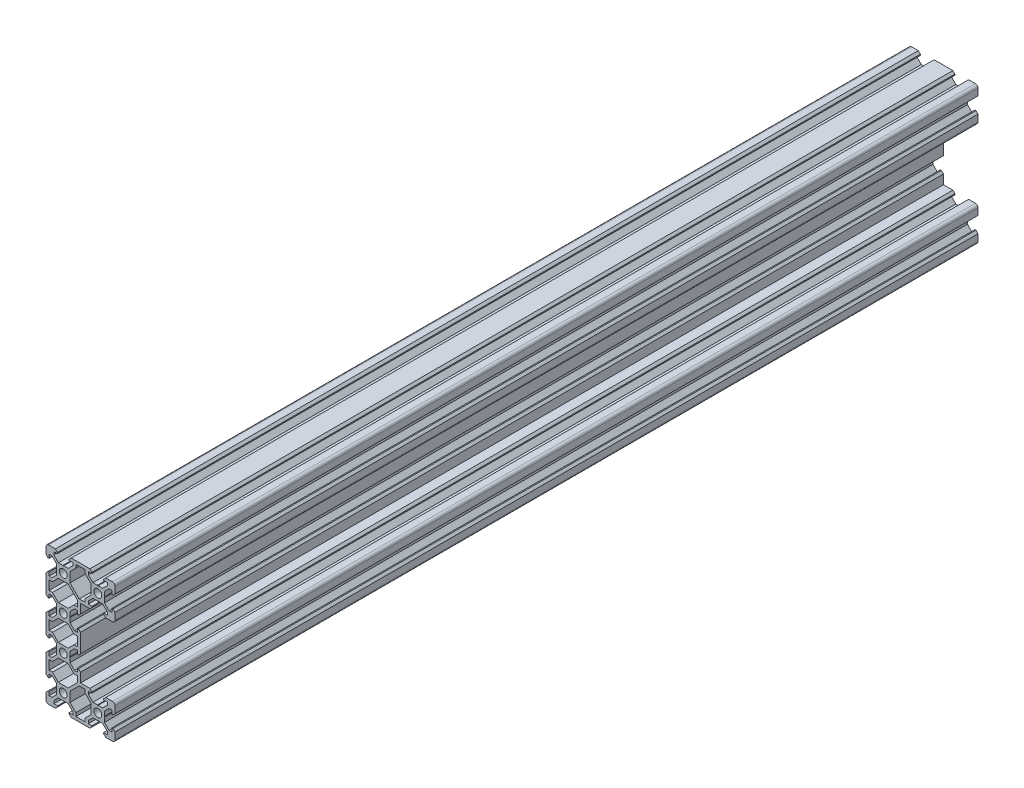
SolidWorks part; units mm, degrees
material "6061-T6 (SS)"
ref_plane "Front Plane" through (0, 0, 0) normal (0, 0, 1) x (1, 0, 0)
ref_plane "Top Plane" through (0, 0, 0) normal (0, 1, 0) x (1, 0, 0)
ref_plane "Right Plane" through (0, 0, 0) normal (1, 0, 0) x (0, 0, -1)
sketch "Sketch1" plane through (0, 0, 0) normal (0, 0, 1) x (1, 0, 0)
  line L0 (-20, -38.5) -> (-20, 38.5)
  line L1 (-18.5, 40) -> (18.5, 40)
  line L2 (20, 38.5) -> (20, 21.5)
  line L3 (18.5, 20) -> (0, 20)
  line L4 (0, 20) -> (0, -20)
  line L5 (0, 0) -> (-20, 0) construction
  line L6 (18.5, -20) -> (0, -20)
  line L7 (20, -38.5) -> (20, -21.5)
  line L8 (-18.5, -40) -> (18.5, -40)
  line L9 (20, 30) -> (10, 30) construction
  line L10 (-10, 0) -> (-10, 10) construction
  arc A0 (-18.5, -40) -> (-20, -38.5) centre (-18.5, -38.5) cw
  arc A1 (20, -38.5) -> (18.5, -40) centre (18.5, -38.5) cw
  arc A2 (18.5, -20) -> (20, -21.5) centre (18.5, -21.5) cw
  arc A3 (20, 21.5) -> (18.5, 20) centre (18.5, 21.5) cw
  arc A4 (18.5, 40) -> (20, 38.5) centre (18.5, 38.5) cw
  arc A5 (-20, 38.5) -> (-18.5, 40) centre (-18.5, 38.5) cw
  circle A6 centre (10, 30) radius 2.3
  circle A7 centre (-10, 30) radius 2.3
  circle A8 centre (-10, 10) radius 2.3
  circle A9 centre (-10, -10) radius 2.3
  circle A10 centre (10, -30) radius 2.3
  circle A11 centre (-10, -30) radius 2.3
  point P13 (-20, -40)
  point P16 (20, -40)
  point P19 (20, -20)
  point P22 (20, 20)
  point P25 (20, 40)
  point P28 (-20, 40)
  line B0 (-10, 30) -> (-10, 40) construction
  line B1 (-10, 33.69) -> (-10.21, 33.9)
  line B2 (-10.21, 33.9) -> (-12.8393, 33.9)
  line B3 (-12.8393, 33.9) -> (-15.5, 36.5607)
  line B4 (-15.5, 36.5607) -> (-15.5, 38.2)
  line B5 (-15.5, 38.2) -> (-13.395, 38.2)
  line B6 (-13.395, 38.2) -> (-13.395, 38.815)
  line B7 (-13.395, 38.815) -> (-14.58, 40)
  line B8 (-14.58, 40) -> (-5.42, 40)
  line B9 (-10, 30) -> (-15.9132, 35.9132) construction
  line B10 (-6.605, 38.815) -> (-5.42, 40)
  line B11 (-6.605, 38.2) -> (-6.605, 38.815)
  line B12 (-4.5, 38.2) -> (-6.605, 38.2)
  line B13 (-4.5, 36.5607) -> (-4.5, 38.2)
  line B14 (-7.1607, 33.9) -> (-4.5, 36.5607)
  line B15 (-9.79, 33.9) -> (-7.1607, 33.9)
  line B16 (-10, 33.69) -> (-9.79, 33.9)
  line B17 (10, 30) -> (10, 40) construction
  line B18 (10, 33.69) -> (9.79, 33.9)
  line B19 (9.79, 33.9) -> (7.1607, 33.9)
  line B20 (7.1607, 33.9) -> (4.5, 36.5607)
  line B21 (4.5, 36.5607) -> (4.5, 38.2)
  line B22 (4.5, 38.2) -> (6.605, 38.2)
  line B23 (6.605, 38.2) -> (6.605, 38.815)
  line B24 (6.605, 38.815) -> (5.42, 40)
  line B25 (5.42, 40) -> (14.58, 40)
  line B26 (10, 30) -> (4.0868, 35.9132) construction
  line B27 (13.395, 38.815) -> (14.58, 40)
  line B28 (13.395, 38.2) -> (13.395, 38.815)
  line B29 (15.5, 38.2) -> (13.395, 38.2)
  line B30 (15.5, 36.5607) -> (15.5, 38.2)
  line B31 (12.8393, 33.9) -> (15.5, 36.5607)
  line B32 (10.21, 33.9) -> (12.8393, 33.9)
  line B33 (10, 33.69) -> (10.21, 33.9)
  line B34 (10, -30) -> (10, -20) construction
  line B35 (10, -26.31) -> (9.79, -26.1)
  line B36 (9.79, -26.1) -> (7.1607, -26.1)
  line B37 (7.1607, -26.1) -> (4.5, -23.4393)
  line B38 (4.5, -23.4393) -> (4.5, -21.8)
  line B39 (4.5, -21.8) -> (6.605, -21.8)
  line B40 (6.605, -21.8) -> (6.605, -21.185)
  line B41 (6.605, -21.185) -> (5.42, -20)
  line B42 (5.42, -20) -> (14.58, -20)
  line B43 (10, -30) -> (4.0868, -24.0868) construction
  line B44 (13.395, -21.185) -> (14.58, -20)
  line B45 (13.395, -21.8) -> (13.395, -21.185)
  line B46 (15.5, -21.8) -> (13.395, -21.8)
  line B47 (15.5, -23.4393) -> (15.5, -21.8)
  line B48 (12.8393, -26.1) -> (15.5, -23.4393)
  line B49 (10.21, -26.1) -> (12.8393, -26.1)
  line B50 (10, -26.31) -> (10.21, -26.1)
  line B51 (-10, 30) -> (-20, 30) construction
  line B52 (-13.69, 30) -> (-13.9, 29.79)
  line B53 (-13.9, 29.79) -> (-13.9, 27.1607)
  line B54 (-13.9, 27.1607) -> (-16.5607, 24.5)
  line B55 (-16.5607, 24.5) -> (-18.2, 24.5)
  line B56 (-18.2, 24.5) -> (-18.2, 26.605)
  line B57 (-18.2, 26.605) -> (-18.815, 26.605)
  line B58 (-18.815, 26.605) -> (-20, 25.42)
  line B59 (-20, 25.42) -> (-20, 34.58)
  line B60 (-10, 30) -> (-15.9132, 24.0868) construction
  line B61 (-18.815, 33.395) -> (-20, 34.58)
  line B62 (-18.2, 33.395) -> (-18.815, 33.395)
  line B63 (-18.2, 35.5) -> (-18.2, 33.395)
  line B64 (-16.5607, 35.5) -> (-18.2, 35.5)
  line B65 (-13.9, 32.8393) -> (-16.5607, 35.5)
  line B66 (-13.9, 30.21) -> (-13.9, 32.8393)
  line B67 (-13.69, 30) -> (-13.9, 30.21)
  line B68 (-10, 10) -> (-20, 10) construction
  line B69 (-13.69, 10) -> (-13.9, 9.79)
  line B70 (-13.9, 9.79) -> (-13.9, 7.1607)
  line B71 (-13.9, 7.1607) -> (-16.5607, 4.5)
  line B72 (-16.5607, 4.5) -> (-18.2, 4.5)
  line B73 (-18.2, 4.5) -> (-18.2, 6.605)
  line B74 (-18.2, 6.605) -> (-18.815, 6.605)
  line B75 (-18.815, 6.605) -> (-20, 5.42)
  line B76 (-20, 5.42) -> (-20, 14.58)
  line B77 (-10, 10) -> (-15.9132, 4.0868) construction
  line B78 (-18.815, 13.395) -> (-20, 14.58)
  line B79 (-18.2, 13.395) -> (-18.815, 13.395)
  line B80 (-18.2, 15.5) -> (-18.2, 13.395)
  line B81 (-16.5607, 15.5) -> (-18.2, 15.5)
  line B82 (-13.9, 12.8393) -> (-16.5607, 15.5)
  line B83 (-13.9, 10.21) -> (-13.9, 12.8393)
  line B84 (-13.69, 10) -> (-13.9, 10.21)
  line B85 (-10, -10) -> (-20, -10) construction
  line B86 (-13.69, -10) -> (-13.9, -10.21)
  line B87 (-13.9, -10.21) -> (-13.9, -12.8393)
  line B88 (-13.9, -12.8393) -> (-16.5607, -15.5)
  line B89 (-16.5607, -15.5) -> (-18.2, -15.5)
  line B90 (-18.2, -15.5) -> (-18.2, -13.395)
  line B91 (-18.2, -13.395) -> (-18.815, -13.395)
  line B92 (-18.815, -13.395) -> (-20, -14.58)
  line B93 (-20, -14.58) -> (-20, -5.42)
  line B94 (-10, -10) -> (-15.9132, -15.9132) construction
  line B95 (-18.815, -6.605) -> (-20, -5.42)
  line B96 (-18.2, -6.605) -> (-18.815, -6.605)
  line B97 (-18.2, -4.5) -> (-18.2, -6.605)
  line B98 (-16.5607, -4.5) -> (-18.2, -4.5)
  line B99 (-13.9, -7.1607) -> (-16.5607, -4.5)
  line B100 (-13.9, -9.79) -> (-13.9, -7.1607)
  line B101 (-13.69, -10) -> (-13.9, -9.79)
  line B102 (-10, -30) -> (-20, -30) construction
  line B103 (-13.69, -30) -> (-13.9, -30.21)
  line B104 (-13.9, -30.21) -> (-13.9, -32.8393)
  line B105 (-13.9, -32.8393) -> (-16.5607, -35.5)
  line B106 (-16.5607, -35.5) -> (-18.2, -35.5)
  line B107 (-18.2, -35.5) -> (-18.2, -33.395)
  line B108 (-18.2, -33.395) -> (-18.815, -33.395)
  line B109 (-18.815, -33.395) -> (-20, -34.58)
  line B110 (-20, -34.58) -> (-20, -25.42)
  line B111 (-10, -30) -> (-15.9132, -35.9132) construction
  line B112 (-18.815, -26.605) -> (-20, -25.42)
  line B113 (-18.2, -26.605) -> (-18.815, -26.605)
  line B114 (-18.2, -24.5) -> (-18.2, -26.605)
  line B115 (-16.5607, -24.5) -> (-18.2, -24.5)
  line B116 (-13.9, -27.1607) -> (-16.5607, -24.5)
  line B117 (-13.9, -29.79) -> (-13.9, -27.1607)
  line B118 (-13.69, -30) -> (-13.9, -29.79)
  line B119 (-10, -30) -> (-10, -40) construction
  line B120 (-10, -33.69) -> (-9.79, -33.9)
  line B121 (-9.79, -33.9) -> (-7.1607, -33.9)
  line B122 (-7.1607, -33.9) -> (-4.5, -36.5607)
  line B123 (-4.5, -36.5607) -> (-4.5, -38.2)
  line B124 (-4.5, -38.2) -> (-6.605, -38.2)
  line B125 (-6.605, -38.2) -> (-6.605, -38.815)
  line B126 (-6.605, -38.815) -> (-5.42, -40)
  line B127 (-5.42, -40) -> (-14.58, -40)
  line B128 (-10, -30) -> (-4.0868, -35.9132) construction
  line B129 (-13.395, -38.815) -> (-14.58, -40)
  line B130 (-13.395, -38.2) -> (-13.395, -38.815)
  line B131 (-15.5, -38.2) -> (-13.395, -38.2)
  line B132 (-15.5, -36.5607) -> (-15.5, -38.2)
  line B133 (-12.8393, -33.9) -> (-15.5, -36.5607)
  line B134 (-10.21, -33.9) -> (-12.8393, -33.9)
  line B135 (-10, -33.69) -> (-10.21, -33.9)
  line B136 (10, -30) -> (10, -40) construction
  line B137 (10, -33.69) -> (10.21, -33.9)
  line B138 (10.21, -33.9) -> (12.8393, -33.9)
  line B139 (12.8393, -33.9) -> (15.5, -36.5607)
  line B140 (15.5, -36.5607) -> (15.5, -38.2)
  line B141 (15.5, -38.2) -> (13.395, -38.2)
  line B142 (13.395, -38.2) -> (13.395, -38.815)
  line B143 (13.395, -38.815) -> (14.58, -40)
  line B144 (14.58, -40) -> (5.42, -40)
  line B145 (10, -30) -> (15.9132, -35.9132) construction
  line B146 (6.605, -38.815) -> (5.42, -40)
  line B147 (6.605, -38.2) -> (6.605, -38.815)
  line B148 (4.5, -38.2) -> (6.605, -38.2)
  line B149 (4.5, -36.5607) -> (4.5, -38.2)
  line B150 (7.1607, -33.9) -> (4.5, -36.5607)
  line B151 (9.79, -33.9) -> (7.1607, -33.9)
  line B152 (10, -33.69) -> (9.79, -33.9)
  line B153 (10, 30) -> (10, 20) construction
  line B154 (10, 26.31) -> (10.21, 26.1)
  line B155 (10.21, 26.1) -> (12.8393, 26.1)
  line B156 (12.8393, 26.1) -> (15.5, 23.4393)
  line B157 (15.5, 23.4393) -> (15.5, 21.8)
  line B158 (15.5, 21.8) -> (13.395, 21.8)
  line B159 (13.395, 21.8) -> (13.395, 21.185)
  line B160 (13.395, 21.185) -> (14.58, 20)
  line B161 (14.58, 20) -> (5.42, 20)
  line B162 (10, 30) -> (15.9132, 24.0868) construction
  line B163 (6.605, 21.185) -> (5.42, 20)
  line B164 (6.605, 21.8) -> (6.605, 21.185)
  line B165 (4.5, 21.8) -> (6.605, 21.8)
  line B166 (4.5, 23.4393) -> (4.5, 21.8)
  line B167 (7.1607, 26.1) -> (4.5, 23.4393)
  line B168 (9.79, 26.1) -> (7.1607, 26.1)
  line B169 (10, 26.31) -> (9.79, 26.1)
  line B170 (-10, 10) -> (0, 10) construction
  line B171 (-6.31, 10) -> (-6.1, 10.21)
  line B172 (-6.1, 10.21) -> (-6.1, 12.8393)
  line B173 (-6.1, 12.8393) -> (-3.4393, 15.5)
  line B174 (-3.4393, 15.5) -> (-1.8, 15.5)
  line B175 (-1.8, 15.5) -> (-1.8, 13.395)
  line B176 (-1.8, 13.395) -> (-1.185, 13.395)
  line B177 (-1.185, 13.395) -> (0, 14.58)
  line B178 (0, 14.58) -> (0, 5.42)
  line B179 (-10, 10) -> (-4.0868, 15.9132) construction
  line B180 (-1.185, 6.605) -> (0, 5.42)
  line B181 (-1.8, 6.605) -> (-1.185, 6.605)
  line B182 (-1.8, 4.5) -> (-1.8, 6.605)
  line B183 (-3.4393, 4.5) -> (-1.8, 4.5)
  line B184 (-6.1, 7.1607) -> (-3.4393, 4.5)
  line B185 (-6.1, 9.79) -> (-6.1, 7.1607)
  line B186 (-6.31, 10) -> (-6.1, 9.79)
  line B187 (-10, -10) -> (0, -10) construction
  line B188 (-6.31, -10) -> (-6.1, -9.79)
  line B189 (-6.1, -9.79) -> (-6.1, -7.1607)
  line B190 (-6.1, -7.1607) -> (-3.4393, -4.5)
  line B191 (-3.4393, -4.5) -> (-1.8, -4.5)
  line B192 (-1.8, -4.5) -> (-1.8, -6.605)
  line B193 (-1.8, -6.605) -> (-1.185, -6.605)
  line B194 (-1.185, -6.605) -> (0, -5.42)
  line B195 (0, -5.42) -> (0, -14.58)
  line B196 (-10, -10) -> (-4.0868, -4.0868) construction
  line B197 (-1.185, -13.395) -> (0, -14.58)
  line B198 (-1.8, -13.395) -> (-1.185, -13.395)
  line B199 (-1.8, -15.5) -> (-1.8, -13.395)
  line B200 (-3.4393, -15.5) -> (-1.8, -15.5)
  line B201 (-6.1, -12.8393) -> (-3.4393, -15.5)
  line B202 (-6.1, -10.21) -> (-6.1, -12.8393)
  line B203 (-6.31, -10) -> (-6.1, -10.21)
  line B204 (10, -30) -> (20, -30) construction
  line B205 (13.69, -30) -> (13.9, -29.79)
  line B206 (13.9, -29.79) -> (13.9, -27.1607)
  line B207 (13.9, -27.1607) -> (16.5607, -24.5)
  line B208 (16.5607, -24.5) -> (18.2, -24.5)
  line B209 (18.2, -24.5) -> (18.2, -26.605)
  line B210 (18.2, -26.605) -> (18.815, -26.605)
  line B211 (18.815, -26.605) -> (20, -25.42)
  line B212 (20, -25.42) -> (20, -34.58)
  line B213 (10, -30) -> (15.9132, -24.0868) construction
  line B214 (18.815, -33.395) -> (20, -34.58)
  line B215 (18.2, -33.395) -> (18.815, -33.395)
  line B216 (18.2, -35.5) -> (18.2, -33.395)
  line B217 (16.5607, -35.5) -> (18.2, -35.5)
  line B218 (13.9, -32.8393) -> (16.5607, -35.5)
  line B219 (13.9, -30.21) -> (13.9, -32.8393)
  line B220 (13.69, -30) -> (13.9, -30.21)
  line B221 (10, 30) -> (20, 30) construction
  line B222 (13.69, 30) -> (13.9, 30.21)
  line B223 (13.9, 30.21) -> (13.9, 32.8393)
  line B224 (13.9, 32.8393) -> (16.5607, 35.5)
  line B225 (16.5607, 35.5) -> (18.2, 35.5)
  line B226 (18.2, 35.5) -> (18.2, 33.395)
  line B227 (18.2, 33.395) -> (18.815, 33.395)
  line B228 (18.815, 33.395) -> (20, 34.58)
  line B229 (20, 34.58) -> (20, 25.42)
  line B230 (10, 30) -> (15.9132, 35.9132) construction
  line B231 (18.815, 26.605) -> (20, 25.42)
  line B232 (18.2, 26.605) -> (18.815, 26.605)
  line B233 (18.2, 24.5) -> (18.2, 26.605)
  line B234 (16.5607, 24.5) -> (18.2, 24.5)
  line B235 (13.9, 27.1607) -> (16.5607, 24.5)
  line B236 (13.9, 29.79) -> (13.9, 27.1607)
  line B237 (13.69, 30) -> (13.9, 29.79)
  line B238 (-18.2, -2.7) -> (-18.2, 2.7)
  line B239 (-18.2, 2.7) -> (-16.2393, 2.7)
  line B240 (-16.2393, 2.7) -> (-12.8393, 6.1)
  line B241 (-12.8393, 6.1) -> (-7.1607, 6.1)
  line B242 (-10, 6.1) -> (-10, 0) construction
  line B243 (-10, 0) -> (-18.2, 0) construction
  line B244 (-3.7607, 2.7) -> (-7.1607, 6.1)
  line B245 (-1.8, 2.7) -> (-3.7607, 2.7)
  line B246 (-1.8, -2.7) -> (-1.8, 2.7)
  line B247 (-1.8, -2.7) -> (-3.7607, -2.7)
  line B248 (-3.7607, -2.7) -> (-7.1607, -6.1)
  line B249 (-12.8393, -6.1) -> (-7.1607, -6.1)
  line B250 (-16.2393, -2.7) -> (-12.8393, -6.1)
  line B251 (-18.2, -2.7) -> (-16.2393, -2.7)
  line B252 (-10, 6.1) -> (-10, 10) construction
  line B253 (-10, 10) -> (-15.0927, 4.9073) construction
  line B254 (-18.2, 17.3) -> (-18.2, 22.7)
  line B255 (-18.2, 22.7) -> (-16.2393, 22.7)
  line B256 (-16.2393, 22.7) -> (-12.8393, 26.1)
  line B257 (-12.8393, 26.1) -> (-7.1607, 26.1)
  line B258 (-10, 26.1) -> (-10, 20) construction
  line B259 (-10, 20) -> (-18.2, 20) construction
  line B260 (-1.8, 17.3) -> (-3.7607, 17.3)
  line B261 (-3.7607, 17.3) -> (-7.1607, 13.9)
  line B262 (-12.8393, 13.9) -> (-7.1607, 13.9)
  line B263 (-16.2393, 17.3) -> (-12.8393, 13.9)
  line B264 (-18.2, 17.3) -> (-16.2393, 17.3)
  line B265 (-10, 26.1) -> (-10, 30) construction
  line B266 (-10, 30) -> (-15.0927, 24.9073) construction
  line B267 (-7.1607, 26.1) -> (-1.8, 20.7393)
  line B268 (-1.8, 17.3) -> (-1.8, 20.7393)
  line B269 (2.7, -38.2) -> (-2.7, -38.2)
  line B270 (-2.7, -38.2) -> (-2.7, -36.2393)
  line B271 (-2.7, -36.2393) -> (-6.1, -32.8393)
  line B272 (-6.1, -32.8393) -> (-6.1, -27.1607)
  line B273 (-6.1, -30) -> (0, -30) construction
  line B274 (0, -30) -> (0, -38.2) construction
  line B275 (2.7, -21.8) -> (2.7, -23.7607)
  line B276 (2.7, -23.7607) -> (6.1, -27.1607)
  line B277 (6.1, -32.8393) -> (6.1, -27.1607)
  line B278 (2.7, -36.2393) -> (6.1, -32.8393)
  line B279 (2.7, -38.2) -> (2.7, -36.2393)
  line B280 (-6.1, -30) -> (-10, -30) construction
  line B281 (-10, -30) -> (-4.9073, -35.0927) construction
  line B282 (-6.1, -27.1607) -> (-0.7393, -21.8)
  line B283 (2.7, -21.8) -> (-0.7393, -21.8)
  line B284 (-18.2, -22.7) -> (-18.2, -17.3)
  line B285 (-18.2, -17.3) -> (-16.2393, -17.3)
  line B286 (-16.2393, -17.3) -> (-12.8393, -13.9)
  line B287 (-12.8393, -13.9) -> (-7.1607, -13.9)
  line B288 (-10, -13.9) -> (-10, -20) construction
  line B289 (-10, -20) -> (-18.2, -20) construction
  line B290 (-12.8393, -26.1) -> (-7.1607, -26.1)
  line B291 (-16.2393, -22.7) -> (-12.8393, -26.1)
  line B292 (-18.2, -22.7) -> (-16.2393, -22.7)
  line B293 (-10, -13.9) -> (-10, -10) construction
  line B294 (-10, -10) -> (-15.0927, -15.0927) construction
  line B295 (-3.7607, -17.3) -> (-7.1607, -13.9)
  line B296 (-1.8, -17.3) -> (-3.7607, -17.3)
  line B297 (-1.8, -17.3) -> (-1.8, -20.7393)
  line B298 (-1.8, -20.7393) -> (-7.1607, -26.1)
  line B299 (-2.7, 38.2) -> (2.7, 38.2)
  line B300 (2.7, 38.2) -> (2.7, 36.2393)
  line B301 (2.7, 36.2393) -> (6.1, 32.8393)
  line B302 (6.1, 32.8393) -> (6.1, 27.1607)
  line B303 (6.1, 30) -> (0, 30) construction
  line B304 (0, 30) -> (0, 38.2) construction
  line B305 (-6.1, 32.8393) -> (-6.1, 27.1607)
  line B306 (-2.7, 36.2393) -> (-6.1, 32.8393)
  line B307 (-2.7, 38.2) -> (-2.7, 36.2393)
  line B308 (6.1, 30) -> (10, 30) construction
  line B309 (10, 30) -> (4.9073, 35.0927) construction
  line B310 (2.7, 23.7607) -> (6.1, 27.1607)
  line B311 (2.7, 21.8) -> (2.7, 23.7607)
  line B312 (2.7, 21.8) -> (-0.7393, 21.8)
  line B313 (-0.7393, 21.8) -> (-6.1, 27.1607)
  dimension "D3" = 1.5
  dimension "D6" = 4.6
  dimension "D7" = 20
  dimension "D8" = 20
  dimension "D1" = 40
  dimension "D2" = 80
  dimension "D4" = 20
  dimension "D5" = 20
sketch_block_instance "V Slot 2-1"
sketch_block "V Slot 2" parameters "D1"=10, "D2"=11, "D3"=4.3, "D4"=1.8, "D5"=0.21, "D6"=45, "D7"=9.16, "D8"=1.5, "D9"=6.79
sketch_block_instance "V Slot 2-2"
sketch_block_instance "V Slot 2-3"
sketch_block_instance "V Slot 2-4"
sketch_block_instance "V Slot 2-5"
sketch_block_instance "V Slot 2-6"
sketch_block_instance "V Slot 2-7"
sketch_block_instance "V Slot 2-8"
sketch_block_instance "V Slot 2-9"
sketch_block_instance "V Slot 2-10"
sketch_block_instance "V Slot 2-11"
sketch_block_instance "V Slot 2-12"
sketch_block_instance "V Slot 2-13"
sketch_block_instance "V Slot 2-14"
sketch_block_instance "Center Cutout 1-1"
sketch_block "Center Cutout 1" parameters "D1"=5.4, "D2"=12.2, "D3"=8.2, "D4"=45, "D5"=10, "D6"=1.5
sketch_block_instance "Corner Cutout 1-1"
sketch_block "Corner Cutout 1" parameters "D1"=5.4, "D2"=12.2, "D3"=8.2, "D4"=45, "D5"=10, "D6"=1.5
sketch_block_instance "Corner Cutout 1-2"
sketch_block_instance "Corner Cutout 2-1"
sketch_block "Corner Cutout 2" parameters "D1"=5.4, "D2"=12.2, "D3"=8.2, "D4"=45, "D5"=10, "D6"=1.5
sketch_block_instance "Corner Cutout 2-2"
extrude "Boss-Extrude1" add sketch "Sketch1" along normal blind 500 contours B237 B222 B223 B224 B225 B226 B227 B228 L2 A4 L1 B27 B28 B29 B30 B31 B32 B33 B18 B19 B20 B21 B22 B23 B24 B10 B11 B12 B13 B14 B15 B16 B1 B2 B3 B4 B5 B6 B7 A5 L0 B61 B62 B63 B64 B65 B66 B67 B52 region at (-19.1056, -36.54, 0)
